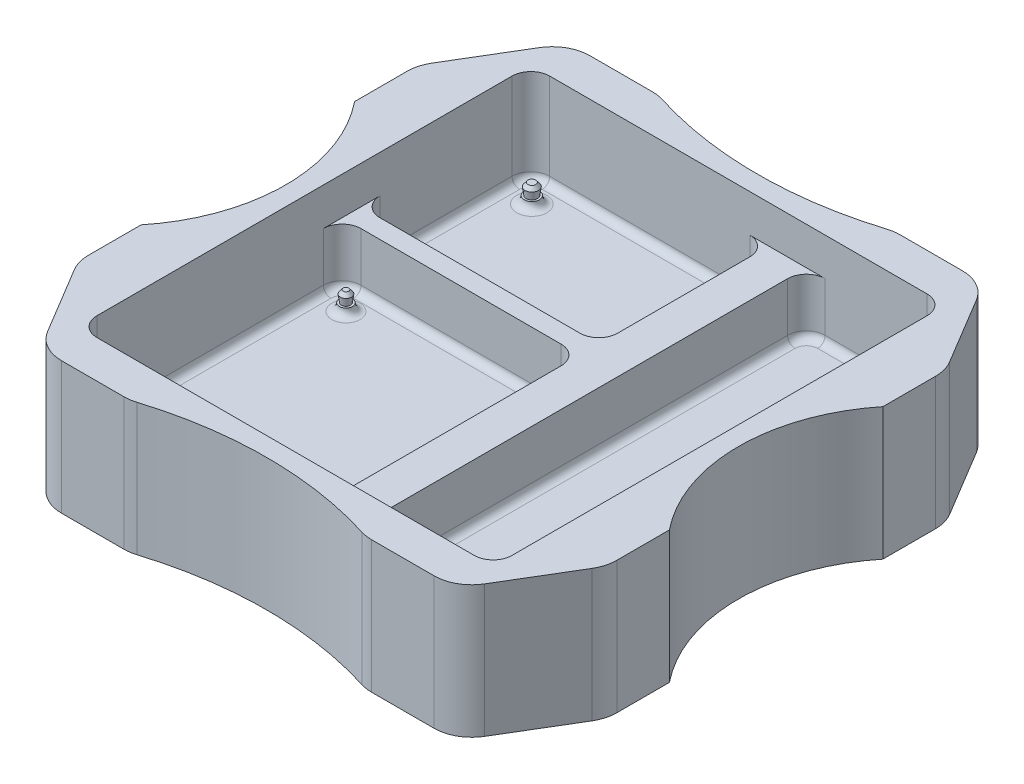
SolidWorks part; units mm, degrees
ref_plane "Front Plane" through (0, 0, 0) normal (0, 0, 1) x (1, 0, 0)
ref_plane "Top Plane" through (0, 0, 0) normal (0, 1, 0) x (1, 0, 0)
ref_plane "Right Plane" through (0, 0, 0) normal (1, 0, 0) x (0, 0, -1)
sketch "Sketch1" plane through (0, 0, 0) normal (0, 1, 0) x (1, 0, 0)
  line L1 (-65.8, 49) -> (74.2, 49)
  line L2 (-65.8, 49) -> (-65.8, -91)
  line L3 (-65.8, -91) -> (74.2, -91)
  line L4 (74.2, 49) -> (74.2, -91)
  dimension "D1" = 140
  dimension "D2" = 140
extrude "Boss-Extrude1" add sketch "Sketch1" along normal blind 40
shell "Shell3" thickness 10 removed face at (4.2, 40, 21)
sketch "Sketch3" plane through (0, 10, 0) normal (0, 1, 0) x (1, 0, 0)
  line L0 (-55.8, -81) -> (64.2, -81) construction
  line L1 (-55.8, 39) -> (-50.8, 39)
  line L2 (-55.8, 39) -> (-55.8, -81)
  line L3 (-55.8, -81) -> (-50.8, -81)
  line L4 (-50.8, 39) -> (-50.8, -81)
  line L5 (64.2, 39) -> (-55.8, 39) construction
  line L6 (64.2, -81) -> (59.2, -81)
  line L7 (64.2, -81) -> (64.2, 39)
  line L8 (64.2, 39) -> (59.2, 39)
  line L9 (59.2, -81) -> (59.2, 39)
  dimension "D1" = 5
  dimension "D2" = 5
extrude "Boss-Extrude2" add sketch "Sketch3" along normal up to surface (30 mm away) up to face at (4.2, 40, 21)
sketch "Sketch4" plane through (0, 40, 0) normal (0, 1, 0) x (1, 0, 0)
  line L0 (-65.8, 24) -> (-50.8, 49)
  line L1 (-65.8, 49) -> (-65.8, -91) construction
  line L2 (74.2, 49) -> (-65.8, 49) construction
  line L3 (-50.8, 49) -> (-65.8, 49)
  line L4 (-65.8, 49) -> (-65.8, 24)
  line L5 (59.2, 49) -> (74.2, 49)
  line L6 (74.2, 49) -> (74.2, 24)
  line L7 (74.2, -91) -> (74.2, 49) construction
  line L8 (74.2, 24) -> (59.2, 49)
  line L9 (74.2, -91) -> (74.2, -66)
  line L10 (74.2, -66) -> (59.2, -91)
  line L11 (-65.8, -91) -> (74.2, -91) construction
  line L12 (59.2, -91) -> (74.2, -91)
  line L13 (-65.8, -66) -> (-50.8, -91)
  line L14 (-50.8, -91) -> (-65.8, -91)
  line L15 (-65.8, -91) -> (-65.8, -66)
  dimension "D1" = 15
  dimension "D2" = 25
  dimension "D3" = 15
  dimension "D4" = 25
  dimension "D5" = 15
  dimension "D6" = 25
  dimension "D7" = 15
  dimension "D8" = 25
extrude "Cut-Extrude1" cut sketch "Sketch4" against normal blind 40
fillet "Fillet1" radius 10 8 edges at (59.2, 20, 91) (74.2, 20, 66) (74.2, 20, -24) (59.2, 20, -49) (-50.8, 20, -49) (-65.8, 20, -24) (-65.8, 20, 66) (-50.8, 20, 91)
sketch "Sketch5" plane through (0, 40, 0) normal (0, 1, 0) x (1, 0, 0)
  line L0 (-65.8, 21.2302) -> (-65.8, -63.2302) construction
  line L1 (-65.8, 21.2302) -> (-65.8, -63.2302) construction
  line L2 (74.2, -63.2302) -> (74.2, 21.2302) construction
  line L3 (53.5381, 49) -> (-45.1381, 49) construction
  line L4 (53.5381, 49) -> (-45.1381, 49) construction
  line L5 (-45.1381, -91) -> (53.5381, -91) construction
  circle A0 centre (-100.8, -21) radius 45
  circle A1 centre (109.2, -21) radius 45
  circle A2 centre (4.2, 144) radius 100
  circle A3 centre (4.2, -186) radius 100
  point P4 (-65.8, -21)
  point P9 (74.2, -21)
  point P14 (4.2, 49)
  point P17 (4.2, 49)
  point P22 (4.2, -91)
  dimension "D1" = 90
  dimension "D4" = 35
  dimension "D5" = 90
  dimension "D7" = 200
  dimension "D6" = 95
  dimension "D2" = 35
  dimension "D3" = 0
  dimension "70" = 95
  dimension "D8" = 0
extrude "Cut-Extrude4" cut sketch "Sketch5" against normal blind 40
fillet "Fillet2" radius 10 4 edges at (-27.025, 20, -49) (35.425, 20, -49) (-27.025, 20, 91) (35.425, 20, 91)
sketch "Sketch6" plane through (0, 10, 0) normal (0, 1, 0) x (1, 0, 0)
  line L0 (-50.8, -81) -> (-50.8, 39) construction
  line L1 (-50.8, -6) -> (12.2, -6)
  line L2 (-50.8, -6) -> (-50.8, -11)
  line L3 (-50.8, -11) -> (12.2, -11)
  line L4 (12.2, -6) -> (12.2, -11)
  line L5 (59.2, 39) -> (-50.8, 39) construction
  line L6 (12.2, 39) -> (22.2, 39)
  line L7 (12.2, 39) -> (12.2, -81)
  line L8 (12.2, -81) -> (22.2, -81)
  line L9 (22.2, 39) -> (22.2, -81)
  line L10 (-50.8, -81) -> (59.2, -81) construction
  line M1 (-50.8, -81) -> (59.2, -81)
  line M3 (59.2, 39) -> (-50.8, 39)
  line M4 (-50.8, 39) -> (-50.8, -81)
  dimension "D1" = 45
  dimension "D2" = 70
  dimension "D3" = 63
  dimension "D4" = 37
extrude "Boss-Extrude3" add sketch "Sketch6" along normal blind 15 contours L4 L1 L3 M4 | L9 L7 L4 M3 M1 region at (-19.3, 10, 8.5) region at (17.2, 10, 21)
fillet "Fillet4" radius 5 12 edges at (59.2, 25, -39) (22.2, 17.5, -39) (59.2, 25, 81) (22.2, 17.5, 81) (12.2, 17.5, 81) (-50.8, 25, 81) (-50.8, 17.5, 11) (12.2, 17.5, 11) (12.2, 17.5, 6) (-50.8, 17.5, 6) (-50.8, 25, -39) (12.2, 17.5, -39)
sketch "Sketch7" plane through (0, 10, 0) normal (0, 1, 0) x (1, 0, 0)
  line L0 (-50.8, -76) -> (-50.8, -16) construction
  line L2 (-45.8, -81) -> (7.2, -81) construction
  line L3 (-45.8, -11) -> (7.2, -11) construction
  line L4 (-45.8, -6) -> (7.2, -6) construction
  line L6 (-50.8, -76) -> (-50.8, 34) construction
  circle A0 centre (-43.8, -75) radius 1.75
  circle A1 centre (5.2, -75) radius 1.75
  circle A2 centre (-43.8, -17) radius 1.75
  circle A3 centre (5.2, -16) radius 1.75
  circle A4 centre (-43.8, 0.75) radius 2
  circle A5 centre (-43.8, 32.25) radius 2
  dimension "D1" = 58
  dimension "D9" = 31.5
  dimension "D12" = 3.5
  dimension "D13" = 3.5
  dimension "D14" = 3.5
  dimension "D15" = 3.5
  dimension "D2" = 0
  dimension "D3" = 49
  dimension "D4" = 0
  dimension "D5" = 59
  dimension "D6" = 7
  dimension "D7" = 6
  dimension "D8" = 6
  dimension "D10" = 6.75
  dimension "D11" = 7
extrude "Boss-Extrude4" add sketch "Sketch7" along normal blind 2
sketch "Sketch8" plane through (0, 12, 0) normal (0, 1, 0) x (1, 0, 0)
  circle A0 centre (-43.8, 32.25) radius 1.5
  circle A1 centre (-43.8, 0.75) radius 1.5
  circle A2 centre (-43.8, -17) radius 1.2
  circle A3 centre (5.2, -16) radius 1.2
  circle A4 centre (5.2, -75) radius 1.2
  circle A5 centre (-43.8, -75) radius 1.2
extrude "Boss-Extrude5" add sketch "Sketch8" along normal blind 3 draft 8 draft outward yes
chamfer "Chamfer1" distance 1 angle 45 6 edges at (-43.8, 15, 76.6216) (5.2, 15, 17.6216) (-43.8, 15, 18.6216) (-43.8, 15, -30.3284) (-43.8, 15, 1.1716) (5.2, 15, 76.6216) first distance on face at (-43.8, 15, 76.6216) first distance on face at (5.2, 15, 17.6216) first distance on face at (-43.8, 15, 18.6216) first distance on face at (-43.8, 15, -30.3284) first distance on face at (-43.8, 15, 1.1716) first distance on face at (5.2, 15, 76.6216)
fillet "Fillet7" radius 2 30 edges at (57.7355, 10, 79.5355) (40.7, 10, 81) (23.6645, 10, 79.5355) (22.2, 10, 21) (23.6645, 10, -37.5355) (40.7, 10, -39) (57.7355, 10, -37.5355) (59.2, 10, 21) (-43.8, 10, -30.25) (-49.3355, 10, 4.5355) (-50.8, 10, -16.5) (-49.3355, 10, -37.5355) (-19.3, 10, -39) (10.7355, 10, -37.5355) (12.2, 10, 46) (10.7355, 10, 4.5355) (-19.3, 10, 6) (-43.8, 10, 1.25) (5.2, 10, 17.75) (5.2, 10, 76.75) (-49.3355, 10, 79.5355) (-50.8, 10, 46) (-49.3355, 10, 12.4645) (-19.3, 10, 11) (10.7355, 10, 12.4645) (12.2, 10, -16.5) (10.7355, 10, 79.5355) (-19.3, 10, 81) (-43.8, 10, 76.75) (-43.8, 10, 18.75)
sketch "Sketch9" plane through (0, 40, 0) normal (0, 1, 0) x (1, 0, 0)
  line L1 (73.2698, 76.0199) -> (-76.4584, 76.0199)
  line L3 (73.2698, -104.2099) -> (-76.4584, -104.2099)
  line L4 (-76.4584, 76.0199) -> (-76.4584, -104.2099)
  line L5 (73.2698, 76.0199) -> (128.6124, 76.0199)
  line L6 (73.2698, -104.2099) -> (73.2698, -125.7287)
  line L7 (73.2698, -125.7287) -> (128.6124, -125.7287)
  line L8 (128.6124, 76.0199) -> (128.6124, -125.7287)
extrude "Cut-Extrude5" cut sketch "Sketch9" against normal blind 5
sketch "Sketch10" plane through (0, 10, 0) normal (0, 1, 0) x (1, 0, 0)
  line L0 (57.2, -76) -> (57.2, 34) construction
  line L1 (25.0787, 36.1213) -> (57.2, 36.1213)
  line L2 (25.0787, 36.1213) -> (25.0787, -45.8023)
  line L3 (25.0787, -45.8023) -> (57.2, -45.8023)
  line L4 (57.2, 36.1213) -> (57.2, -45.8023)
  line L6 (-47.9213, 36.1213) -> (9.3213, 36.1213)
  line L7 (-47.9213, 36.1213) -> (-47.9213, -3.1213)
  line L8 (-47.9213, -3.1213) -> (9.3213, -3.1213)
  line L9 (9.3213, 36.1213) -> (9.3213, -3.1213)
  line L10 (-49.3355, -12.4645) -> (11.3498, -12.4645)
  line L11 (-49.3355, -12.4645) -> (-49.3355, -78.7891)
  line L12 (-49.3355, -78.7891) -> (11.3498, -78.7891)
  line L13 (11.3498, -12.4645) -> (11.3498, -78.7891)
  arc A0 (27.2, 37) -> (24.2, 34) centre (27.2, 34) ccw construction
  arc A1 (-45.8, 37) -> (-48.8, 34) centre (-45.8, 34) ccw construction
  arc A2 (7.2, -4) -> (10.2, -1) centre (7.2, -1) ccw construction
  arc A3 (-45.8, -11) -> (-50.8, -16) centre (-45.8, -16) ccw construction
  arc A4 (7.2, -81) -> (12.2, -76) centre (7.2, -76) ccw construction
